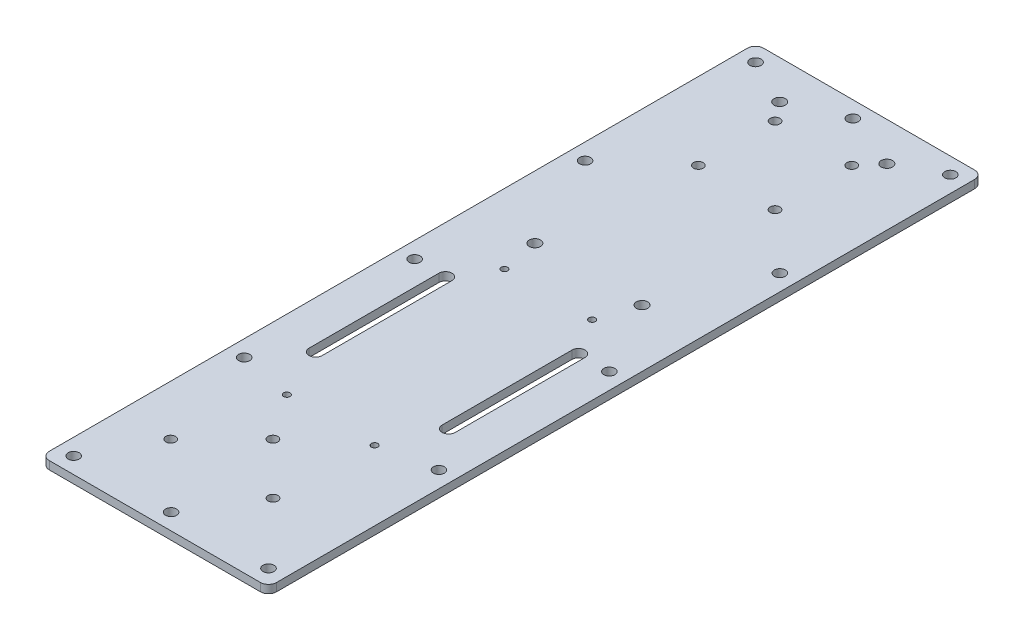
SolidWorks part; units mm, degrees
ref_plane "Front Plane" through (0, 0, 0) normal (0, 0, 1) x (1, 0, 0)
ref_plane "Top Plane" through (0, 0, 0) normal (0, 1, 0) x (1, 0, 0)
ref_plane "Right Plane" through (0, 0, 0) normal (1, 0, 0) x (0, 0, -1)
sketch "Sketch2" plane through (0, 0, 0) normal (0, 1, 0) x (1, 0, 0)
  line L0 (-44.45, 0) -> (44.45, 0) construction
  line L1 (-41.275, 139.7) -> (41.275, 139.7)
  line L2 (-44.45, 136.525) -> (-44.45, -136.525)
  line L3 (-41.275, -139.7) -> (41.275, -139.7)
  line L4 (44.45, 136.525) -> (44.45, -136.525)
  line L5 (0, 139.7) -> (0, -139.7) construction
  arc A0 (-44.45, -136.525) -> (-41.275, -139.7) centre (-41.275, -136.525) ccw
  arc A1 (41.275, -139.7) -> (44.45, -136.525) centre (41.275, -136.525) ccw
  arc A2 (41.275, 139.7) -> (44.45, 136.525) centre (41.275, 136.525) cw
  arc A3 (-41.275, 139.7) -> (-44.45, 136.525) centre (-41.275, 136.525) ccw
  point P8 (0, 0)
  point P13 (-44.45, -139.7)
  point P16 (44.45, -139.7)
  point P21 (-44.45, 139.7)
  dimension "D3" = 3.175
  dimension "D1" = 279.4
  dimension "D2" = 88.9
extrude "Plate Thickness" add sketch "Sketch2" along normal blind 3.175 contours L2 A0 L3 A1 L4 A2 L1 A3
sketch "Sketch3" plane through (0, 3.175, 0) normal (0, 1, 0) x (1, 0, 0)
  line L0 (-44.45, 136.525) -> (-44.45, -136.525) construction
  line L1 (-41.275, 139.7) -> (41.275, 139.7) construction
  line L4 (0, 139.7) -> (0, -139.7) construction
  line L5 (-41.275, -139.7) -> (41.275, -139.7) construction
  circle A0 centre (-38.1, 133.35) radius 2.159
  circle A1 centre (-38.1, 66.675) radius 2.159
  circle A2 centre (-38.1, -66.675) radius 2.159
  circle A3 centre (-38.1, -133.35) radius 2.159
  circle A4 centre (38.1, -133.35) radius 2.159
  circle A5 centre (38.1, -66.675) radius 2.159
  circle A6 centre (38.1, 66.675) radius 2.159
  circle A7 centre (38.1, 133.35) radius 2.159
  circle A8 centre (0, 133.35) radius 2.159
  circle A9 centre (0, -133.35) radius 2.159
  circle A10 centre (-38.1, 0) radius 2.159
  circle A11 centre (38.1, 0) radius 2.159
  dimension "D1" = 4.318
  dimension "D4" = 4.318
  dimension "D2" = 6.35
  dimension "D3" = 6.35
  dimension "D5" = 66.675
  dimension "D6" = 6.35
  dimension "D7" = 66.675
extrude "Mounting holes" cut sketch "Sketch3" against normal through all
sketch "Sketch4" plane through (0, 3.175, 0) normal (0, 1, 0) x (1, 0, 0)
  line L0 (-19.9374, 28.8942) -> (21.9726, 28.8942) construction
  line L1 (1.0176, 0) -> (1.0176, 139.7) construction
  circle A0 centre (-19.9374, 124.6522) radius 2.2225
  circle A1 centre (-19.9374, 28.8942) radius 2.2225
  circle A2 centre (21.9726, 28.8942) radius 2.2225
  circle A3 centre (21.9726, 124.6522) radius 2.2225
  point P13 (1.0176, 28.8942)
  dimension "D1" = 4.445
  dimension "D2" = 95.758
  dimension "D3" = 41.91
extrude "Jetson Holes (w/ mount)" cut sketch "Sketch4" against normal through all
sketch "Sketch5" plane through (0, 3.175, 0) normal (0, 1, 0) x (1, 0, 0)
  circle A1 centre (-14.3419, 117.2351) radius 1.905
  circle A3 centre (15.6555, 117.2351) radius 1.905
  circle A4 centre (15.6555, 87.2377) radius 1.905
  circle A5 centre (-14.3419, 87.2377) radius 1.905
  dimension "D1" = 3.81
  dimension "D2" = 29.9974
  dimension "D3" = 29.9974
extrude "PDB holes" cut sketch "Sketch5" against normal through all
sketch "Sketch6" plane through (0, 3.175, 0) normal (0, 1, 0) x (1, 0, 0)
  circle A3 centre (-24.7939, -108.7175) radius 1.905
  circle A4 centre (15.2111, -108.7175) radius 1.905
  circle A5 centre (-4.8041, -88.7277) radius 1.905
  dimension "D1" = 3.81
  dimension "D2" = 40.005
  dimension "D3" = 19.9898
  dimension "D4" = 19.9898
extrude "Lidar Holes" cut sketch "Sketch6" against normal through all
sketch "Sketch7" plane through (0, 3.175, 0) normal (0, 1, 0) x (1, 0, 0)
  line L0 (0, 139.7) -> (0, -139.7) construction
  line L1 (-41.275, 139.7) -> (41.275, 139.7) construction
  line L2 (-41.275, -139.7) -> (41.275, -139.7) construction
  line L3 (17.145, 14.1724) -> (-17.145, 14.1724) construction
  circle A0 centre (-17.145, 14.1724) radius 1.27
  circle A1 centre (-17.145, -70.9176) radius 1.27
  circle A2 centre (17.145, -70.9176) radius 1.27
  circle A3 centre (17.145, 14.1724) radius 1.27
  point P14 (0, 14.1724)
  dimension "D1" = 2.54
  dimension "D2" = 85.09
  dimension "D3" = 34.29
extrude "PixHawk Holes" cut sketch "Sketch7" against normal through all
sketch "Sketch8" plane through (0, 3.175, 0) normal (0, 1, 0) x (1, 0, 0)
  line L0 (0, 139.7) -> (0, -115.5095) construction
  line L1 (-41.275, 139.7) -> (41.275, 139.7) construction
  line L2 (-26.035, -0.006) -> (-26.035, -50.806) construction
  line L3 (-23.495, -0.006) -> (-23.495, -50.806)
  line L4 (-28.575, -0.006) -> (-28.575, -50.806)
  line L5 (26.035, -0.006) -> (26.035, -50.806) construction
  line L6 (23.495, -0.006) -> (23.495, -50.806)
  line L7 (28.575, -0.006) -> (28.575, -50.806)
  arc A0 (-23.495, -0.006) -> (-28.575, -0.006) centre (-26.035, -0.006) ccw
  arc A1 (-28.575, -50.806) -> (-23.495, -50.806) centre (-26.035, -50.806) ccw
  arc A2 (23.495, -0.006) -> (28.575, -0.006) centre (26.035, -0.006) cw
  arc A3 (28.575, -50.806) -> (23.495, -50.806) centre (26.035, -50.806) cw
  point P7 (-26.035, -25.406)
  point P14 (26.035, -25.406)
  dimension "D1" = 50.8
  dimension "D2" = 5.08
  dimension "D3" = 26.035
extrude "Battery Holes" cut sketch "Sketch8" against normal through all
